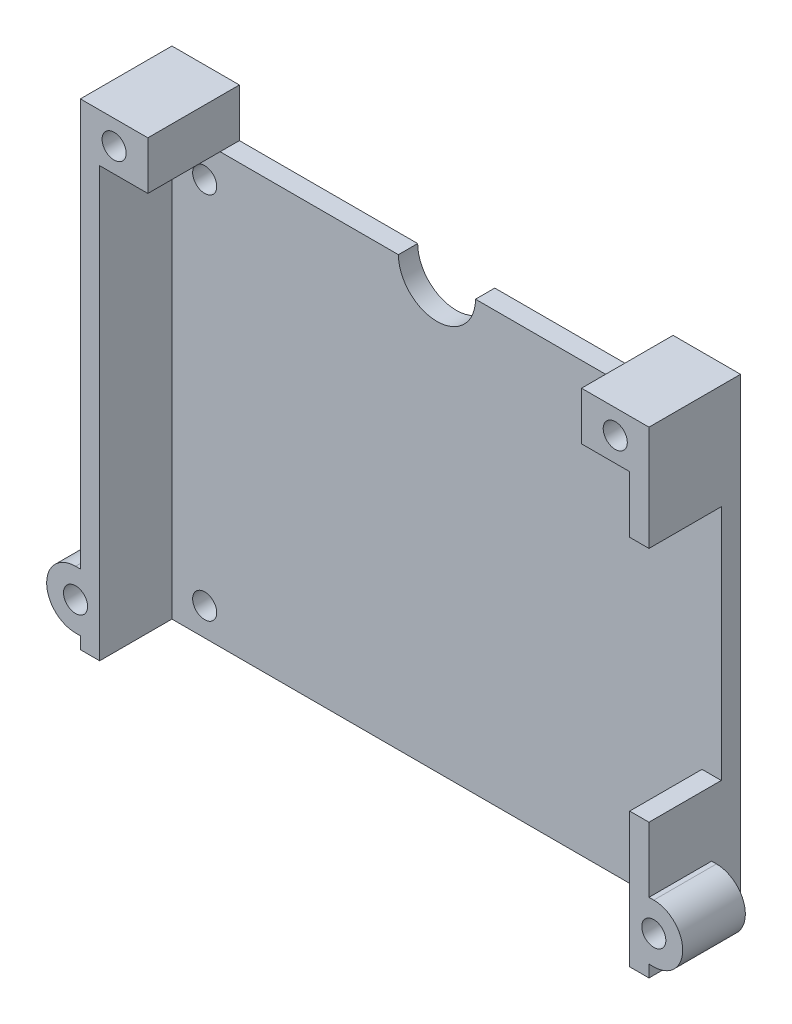
SolidWorks part; units mm, degrees
ref_plane "Front Plane" through (0, 0, 0) normal (0, 0, 1) x (1, 0, 0)
ref_plane "Top Plane" through (0, 0, 0) normal (0, 1, 0) x (1, 0, 0)
ref_plane "Right Plane" through (0, 0, 0) normal (1, 0, 0) x (0, 0, -1)
sketch "Sketch1" plane through (0, 0, 0) normal (0, 1, 0) x (1, 0, 0)
  line L0 (0, 0) -> (2, 0)
  line L1 (0, 0) -> (59, 0) construction
  line L2 (0, 0) -> (0, 9.5)
  line L3 (0, 9.5) -> (59, 9.5)
  line L4 (59, 0) -> (59, 9.5)
  line L5 (2, 0) -> (2, 7.5)
  line L6 (2, 7.5) -> (57, 7.5)
  line L7 (57, 7.5) -> (57, 0)
  line L8 (57, 0) -> (59, 0)
  dimension "D1" = 59
  dimension "D2" = 9.5
  dimension "D3" = 2
  dimension "D4" = 7.5
  dimension "D5" = 55
extrude "Boss-Extrude1" add sketch "Sketch1" along normal blind 44.5
sketch "Sketch2" plane through (59, 0, 0) normal (1, 0, 0) x (0, 0, -1)
  line L0 (0, 0) -> (0, 14) construction
  line L1 (0, 44.5) -> (0, 0) construction
  line L2 (0, 14) -> (7.5, 14)
  line L3 (7.5, 14) -> (7.5, 38.6)
  line L4 (7.5, 38.6) -> (0, 38.6)
  line L5 (0, 38.6) -> (0, 14)
  dimension "D1" = 14
  dimension "D2" = 7.5
  dimension "D3" = 24.6
extrude "Cut-Extrude1" cut sketch "Sketch2" against normal blind 10
sketch "Sketch3" plane through (0, 0, -9.5) normal (0, 0, -1) x (-1, 0, 0)
  line L0 (-59, 0) -> (-59, 7.25) construction
  line L1 (-59, 44.5) -> (-59, 0) construction
  line L2 (-59, 7.25) -> (-59, 1.25)
  line L3 (-59, 4.25) -> (-59.5, 4.25) construction
  line L4 (-59, 7.25) -> (-59.5, 7.25)
  line L5 (-59, 1.25) -> (-59.5, 1.25)
  line L6 (0, 0) -> (0, 7.25) construction
  line L7 (0, 44.5) -> (0, 0) construction
  line L8 (0, 7.25) -> (0.5, 7.25)
  line L9 (0, 7.25) -> (0, 1.25)
  line L10 (0, 1.25) -> (0.5, 1.25)
  line L11 (0, 4.25) -> (0.5, 4.25) construction
  arc A0 (-59.5, 7.25) -> (-59.5, 1.25) centre (-59.5, 4.25) ccw
  circle A1 centre (-59.5, 4.25) radius 1.25
  arc A2 (0.5, 7.25) -> (0.5, 1.25) centre (0.5, 4.25) cw
  circle A3 centre (0.5, 4.25) radius 1.25
  line M5 (0, 0) -> (0, 44.5)
  line M7 (-59, 44.5) -> (-59, 0)
  dimension "D4" = 3
  dimension "D5" = 2.5
  dimension "D11" = 3
  dimension "D12" = 2.5
  dimension "D1" = 7.25
  dimension "D2" = 6
  dimension "D3" = 0.5
  dimension "D6" = 7.25
  dimension "D7" = 0.5
  dimension "D8" = 6
  dimension "D9" = 0.5
extrude "Boss-Extrude2" add sketch "Sketch3" against normal blind 9.5 contours A1 L4 A0 L5 M7 | A3 L10 A2 L8 M5 region at (59.0695, 6.3228, -9.5) region at (-0.25, 7.1805, -9.5)
extrude "Cut-Extrude2" cut sketch "Sketch3<3>" against normal blind 11 contours L2 A1 | L9 A3 region at (58.6906, 4.25, -9.5) region at (0.3094, 4.25, -9.5)
sketch "Sketch3<3>" plane through (0, 0, -9.5) normal (0, 0, -1) x (-1, 0, 0) same geometry as "Sketch3"
sketch "Sketch4" plane through (0, 44.5, 0) normal (0, 1, 0) x (1, 0, 0)
  line L0 (59, 9.5) -> (0, 9.5) construction
  line L1 (0, 0) -> (7, 0)
  line L2 (0, 0) -> (0, 9.5)
  line L3 (0, 9.5) -> (7, 9.5)
  line L4 (7, 0) -> (7, 9.5)
  line L6 (59, 0) -> (52, 0)
  line L7 (59, 0) -> (59, 9.5)
  line L8 (59, 9.5) -> (52, 9.5)
  line L9 (52, 0) -> (52, 9.5)
  dimension "D1" = 7
  dimension "D2" = 7
extrude "Boss-Extrude3" add sketch "Sketch4" along normal blind 5
sketch "Sketch5" plane through (0, 0, -9.5) normal (0, 0, -1) x (-1, 0, 0)
  line L0 (-59, 49.5) -> (-52, 44.5) construction
  line L1 (0, 49.5) -> (-7, 44.5) construction
  circle A0 centre (-55.5, 47) radius 1.25
  circle A1 centre (-3.5, 47) radius 1.25
  dimension "D1" = 2.5
  dimension "D2" = 2.5
extrude "Cut-Extrude3" cut sketch "Sketch5" against normal through all
sketch "Sketch7" plane through (0, 0, -9.5) normal (0, 0, -1) x (-1, 0, 0)
  line L0 (-59, 0) -> (-59, 2.9) construction
  line L1 (-59, 1.25) -> (-59, 0) construction
  line L2 (-59, 2.9) -> (0, 2.9) construction
  line L3 (0, 1.25) -> (0, 0) construction
  line L4 (-53.6, 2.9) -> (-5.4, 2.9)
  line L5 (-53.6, 2.9) -> (-53.6, 41.2) construction
  line L6 (-53.6, 41.2) -> (-5.4, 41.2) construction
  circle A0 centre (-53.6, 2.9) radius 1.25
  circle A1 centre (-5.4, 2.9) radius 1.25
  circle A2 centre (-53.6, 41.2) radius 1.25
  circle A3 centre (-5.4, 41.2) radius 1.25
  point P11 (-29.5, 2.9)
  dimension "D3" = 2.5
  dimension "D4" = 2.5
  dimension "D6" = 2.5
  dimension "D8" = 2.5
  dimension "D1" = 2.9
  dimension "D2" = 48.2
  dimension "D5" = 38.3
  dimension "D7" = 48.2
extrude "Cut-Extrude4" cut sketch "Sketch7" against normal blind 10 contours A2 | A3 | A1 | A0 region at (5.4, 4.1146, -9.5) region at (54.8146, 2.9, -9.5) region at (53.6, 41.2, -9.5) region at (5.4, 41.2, -9.5)
sketch "Sketch8" plane through (0, 0, -9.5) normal (0, 0, -1) x (-1, 0, 0)
  line L0 (-52, 44.5) -> (-7, 44.5) construction
  circle A0 centre (-29.5, 44.5) radius 4
  dimension "D1" = 8
extrude "Cut-Extrude5" cut sketch "Sketch8" against normal through all
extrude "Cut-Extrude6" cut sketch "Sketch3<4>" against normal blind 3 contours A1 L4 A0 L5 M7 | A3 L10 A2 L8 M5 region at (59.0695, 6.3228, -9.5) region at (-0.25, 7.1805, -9.5)
sketch "Sketch3<4>" plane through (0, 0, -9.5) normal (0, 0, -1) x (-1, 0, 0) same geometry as "Sketch3"
extrude "Boss-Extrude4" add sketch "Sketch3<5>" against normal blind 3 contours L9 A3 | L2 A1 region at (58.6906, 4.25, -9.5) region at (0.3094, 4.25, -9.5)
sketch "Sketch3<5>" plane through (0, 0, -9.5) normal (0, 0, -1) x (-1, 0, 0) same geometry as "Sketch3"
